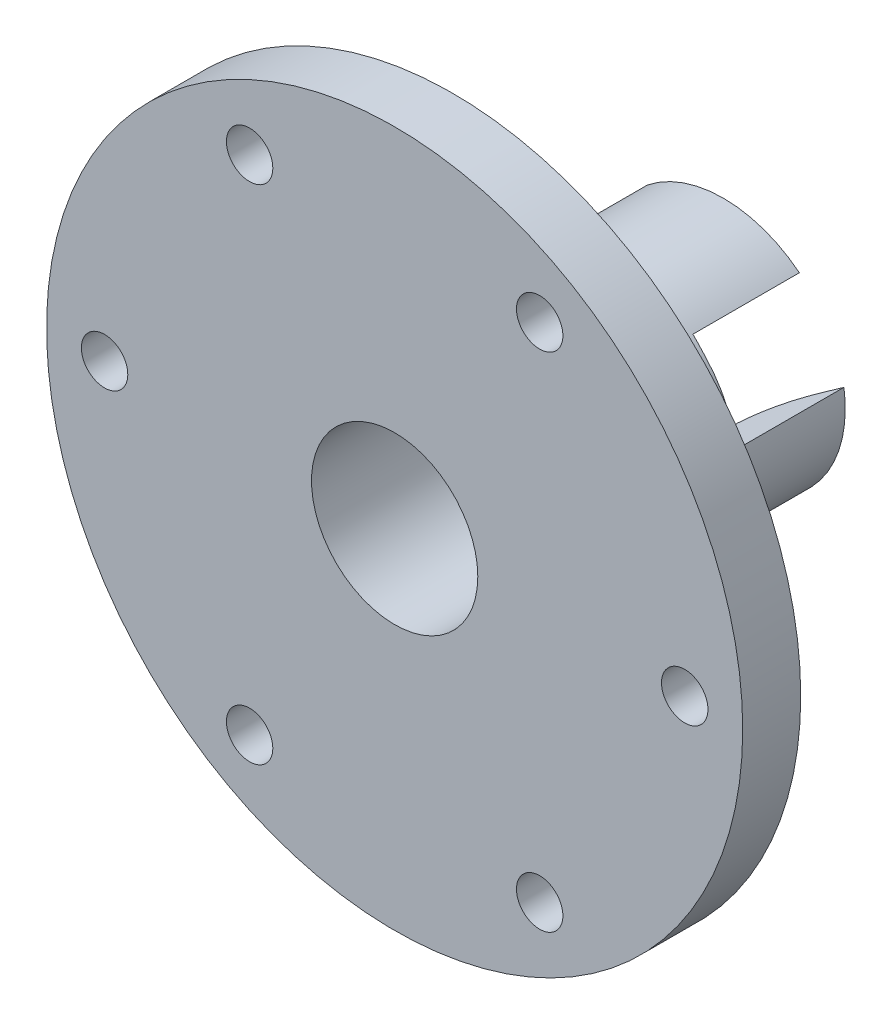
SolidWorks part; units mm, degrees
ref_plane "Front Plane" through (0, 0, 0) normal (0, 0, 1) x (1, 0, 0)
ref_plane "Top Plane" through (0, 0, 0) normal (0, 1, 0) x (1, 0, 0)
ref_plane "Right Plane" through (0, 0, 0) normal (1, 0, 0) x (0, 0, -1)
sketch "Sketch1" plane through (0, 0, 0) normal (0, 0, 1) x (1, 0, 0)
  circle A4 centre (0, 0) radius 10
  circle A5 centre (0, 0) radius 18
  dimension "D1" = 20
  dimension "D2" = 8
extrude "Boss-Extrude1" add sketch "Sketch1" along normal blind 3 contours A5 A4 | A4 region at (0, 0, 0) region at (-17.4909, 0, 0)
hole_wizard "M2 Clearance Hole2" positions "Sketch4" profile "Sketch5" hole size "M2" standard "ANSI Metric" end condition up to next
sketch "Sketch4" plane through (0, 0, 0) normal (0, 0, -1) x (-1, 0, 0)
  circle A3 centre (0, 0) radius 15
  point P42 (-15, 0)
  point P48 (-7.5, 12.9904)
  point P49 (7.5, 12.9904)
  point P50 (15, 0)
  point P51 (7.5, -12.9904)
  point P52 (-7.5, -12.9904)
  dimension "D1" = 30
sketch "Sketch5" plane through (7.5, -12.9904, 0) normal (1, 0, 0) x (0, 1, 0)
  line L0 (0, 0) -> (0, 3)
  line L1 (0, 3) -> (1.2, 3)
  line L2 (1.2, 3) -> (1.2, 0)
  line L5 (1.2, 0) -> (0, 0)
  line L11 (0, -6.35) -> (0, 107.95) construction
  dimension "Thru Hole Dia." = 2.4
  dimension "Thru Hole Depth" = 3
sketch "Sketch6" plane through (0, 0, 0) normal (0, 0, 1) x (1, 0, 0)
  circle A0 centre (0, 0) radius 6.3
  circle A1 centre (0, 0) radius 4.3
  circle A2 centre (0, 0) radius 9.3
  dimension "D1" = 12.6
  dimension "D2" = 2
  dimension "D3" = 3
extrude "Boss-Extrude2" add sketch "Sketch6" against normal blind 15 contours A0 A1 region at (-6.1218, 0, 0)
extrude "Cut-Extrude2" cut sketch "Sketch6<2>" along normal through all contours A1 region at (0, 0, 0)
sketch "Sketch6<2>" plane through (0, 0, 0) normal (0, 0, 1) x (1, 0, 0) same geometry as "Sketch6"
extrude "Boss-Extrude3" add sketch "Sketch6<4>" against normal blind 2.5 contours A2 A0 region at (-9.037, 0, 0)
sketch "Sketch6<4>" plane through (0, 0, 0) normal (0, 0, 1) x (1, 0, 0) same geometry as "Sketch6"
chamfer "Chamfer1" distance 1 angle 45 1 edges at (9.3, 0, -2.5)
sketch "Sketch7" plane through (0, 0, 3) normal (0, 0, 1) x (1, 0, 0)
  circle A0 centre (0, 0) radius 21
  circle A1 centre (0, 0) radius 22.5
  dimension "D1" = 42
  dimension "D2" = 1.5
extrude "Boss-Extrude4" [suppressed] add sketch "Sketch7" along normal blind 1
chamfer "Chamfer2" distance 3 angle 45 1 edges at (4.3, 0, -15)
sketch "Sketch8" plane through (0, 0, -2.5) normal (0, 0, -1) x (-1, 0, 0)
  line L0 (0, -10.8928) -> (0, 0) construction
  line L1 (0, 0) -> (-11.1503, 6.4377) construction
  line L2 (0, 0) -> (11.0083, 6.3556) construction
  line L3 (-6.2294, 0.9407) -> (-4.2966, 0.1712)
  line L4 (-3.9294, 4.9244) -> (-2.2966, 3.6353)
  arc A0 (-6.2294, 0.9407) -> (-3.9294, 4.9244) centre (0, 0) cw
  circle A2 centre (0, 0) radius 6.3 construction
  arc A3 (-4.2966, 0.1712) -> (-2.2966, 3.6353) centre (0, 0) cw
  circle A4 centre (0, 0) radius 4.3 construction
  dimension "D3" = 4.6
  dimension "D1" = 120
  dimension "D2" = 120
  dimension "D4" = 4
extrude "Cut-Extrude3" cut sketch "Sketch8" along normal blind 16 from offset 6
pattern_circular "CirPattern1" count 3 over 360 about axis through (0, 0, -12) along (0, 0, -1) of "Cut-Extrude3"
chamfer "Chamfer3" distance 3 angle 30 3 edges at (3.7239, 2.15, -8.5) (0, -4.3, -8.5) (-3.7239, 2.15, -8.5) first distance on face at (4.3, 0, 3)
fillet "Fillet2" radius 5 3 edges at (-3.7239, -2.15, -12) (3.7239, -2.15, -12) (0, 4.3, -12)
fillet "Fillet3" radius 1 6 edges
fillet "Fillet4" radius 1 9 edges at (-1.9053, -5.5086, -8.5) (1.8749, -5.5481, -8.5) (-3.8179, 4.4043, -8.5) (-5.7423, 1.1503, -8.5) (5.7232, 1.1042, -8.5) (3.8674, 4.3978, -8.5) (0, -6.0321, -8.5) (-5.2239, 3.016, -8.5) (5.2239, 3.016, -8.5)
